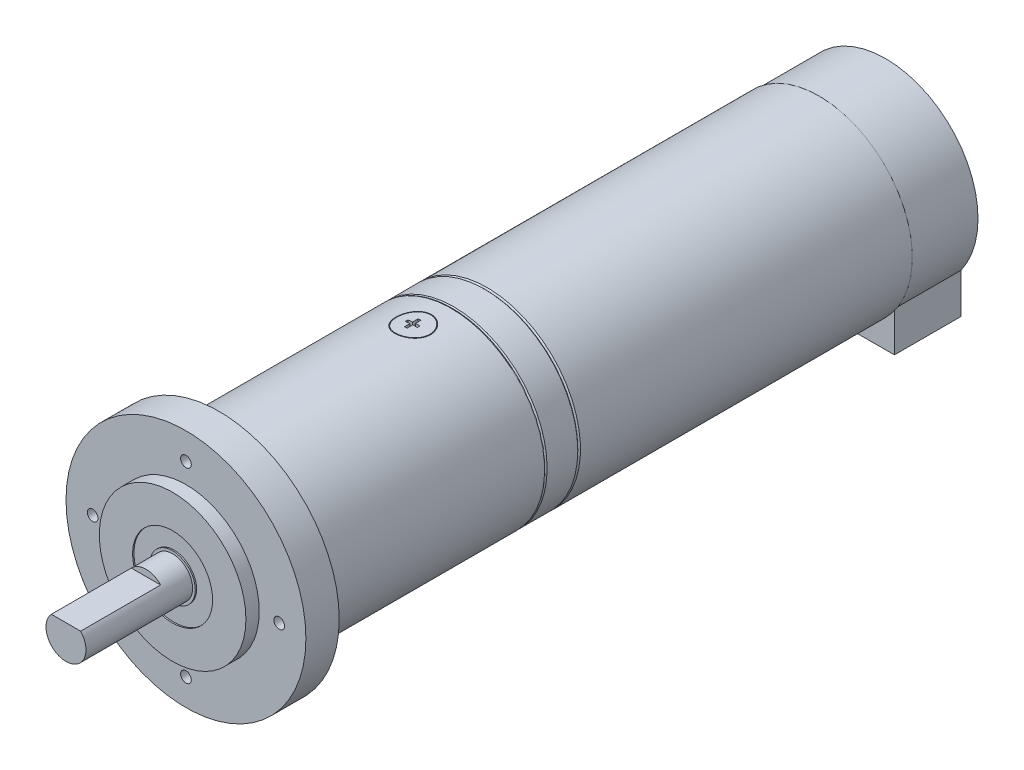
SolidWorks part; units mm, degrees
ref_plane "Front Plane" through (0, 0, 0) normal (0, 0, 1) x (1, 0, 0)
ref_plane "Top Plane" through (0, 0, 0) normal (0, 1, 0) x (1, 0, 0)
ref_plane "Right Plane" through (0, 0, 0) normal (1, 0, 0) x (0, 0, -1)
sketch "Sketch1" plane through (0, 0, 0) normal (0, 0, 1) x (1, 0, 0)
  circle A0 centre (0, 0) radius 18
  circle A1 centre (0, 0) radius 11
  dimension "D1" = 36
  dimension "D2" = 22
extrude "Boss-Extrude2" add sketch "Sketch1" against normal blind 5 contours A0
extrude "Boss-Extrude3" add sketch "Sketch1<4>" along normal blind 2 contours A1
sketch "Sketch1<4>" plane through (0, 0, 0) normal (0, 0, 1) x (1, 0, 0) same geometry as "Sketch1"
sketch "Sketch2" plane through (0, 0, 2) normal (0, 0, 1) x (1, 0, 0)
  circle A0 centre (0, 0) radius 3
  dimension "D1" = 6
extrude "Boss-Extrude4" add sketch "Sketch2" along normal blind 16 contours A0
sketch "Sketch3" plane through (0, 0, 18) normal (0, 0, 1) x (1, 0, 0)
  line L1 (-2.9161, 3.7933) -> (3.4469, 3.7933)
  line L2 (-2.9161, 3.7933) -> (-2.9161, 2.0435)
  line L3 (-2.9161, 2.0435) -> (3.4469, 2.0435)
  line L4 (3.4469, 3.7933) -> (3.4469, 2.0435)
extrude "Cut-Extrude1" cut sketch "Sketch3" against normal blind 12
sketch "Sketch4" plane through (0, 0, 2) normal (0, 0, 1) x (1, 0, 0)
  circle A0 centre (0, 0) radius 6
  circle A1 centre (0, 0) radius 3.4
  dimension "D1" = 12
  dimension "D2" = 6.8
extrude "Cut-Extrude2" cut sketch "Sketch4" against normal blind 0.2
sketch "Sketch5" plane through (0, 0, -5) normal (0, 0, -1) x (-1, 0, 0)
  circle A0 centre (0, 0) radius 14
  point P3 (0, 14)
  point P4 (-14, 0)
  point P5 (0, -14)
  point P6 (14, 0)
hole_wizard "Tap Drill for M2x0.4 Tap1" positions "3DSketch1" profile "Sketch6" hole size "M2x0.4" standard "ANSI Metric" end condition through all
sketch3d "3DSketch1"
  point P0 (0, 14, -5)
  point P3 (14, 0, -5)
  point P6 (0, -14, -5)
  point P9 (-14, 0, -5)
sketch "Sketch6" plane through (0, 14, -5) normal (1, 0, 0) x (0, 1, 0)
  line L0 (0, 0) -> (0, 23)
  line L1 (0, 23) -> (0.8, 23)
  line L2 (0.8, 23) -> (0.8, 0)
  line L5 (0.8, 0) -> (0, 0)
  line L11 (0, -6.35) -> (0, 107.95) construction
  dimension "Thru Hole Dia." = 1.6
  dimension "Thru Hole Depth" = 23
extrude "Boss-Extrude5" add sketch "Sketch5" along normal blind 35 contours A0
fillet "Fillet2" radius 0.2 1 edges at (-14, 0, -40)
sketch "Sketch7" plane through (0, 0, -40) normal (0, 0, -1) x (-1, 0, 0)
  circle A0 centre (0, 0) radius 14
extrude "Boss-Extrude6" add sketch "Sketch7" along normal blind 5
chamfer "Chamfer1" distance 0.2 angle 45 2 edges at (-14, 0, -45) (-14, 0, -40)
sketch "Sketch10" plane through (0, 0, -45) normal (0, 0, -1) x (-1, 0, 0)
  circle A0 centre (0, 0) radius 14
extrude "Boss-Extrude7" add sketch "Sketch10" along normal blind 50
chamfer "Chamfer2" distance 0.2 angle 45 1 edges at (-14, 0, -45)
sketch "Sketch11" plane through (0, 0, -95) normal (0, 0, -1) x (-1, 0, 0)
  line L2 (-11.3137, -8) -> (-11.3137, -14)
  line L3 (-11.3137, -14) -> (11.3137, -14)
  line L4 (11.3137, -8) -> (11.3137, -14)
  arc A0 (11.3137, -8) -> (-11.3137, -8) centre (0, 0) ccw
  circle A1 centre (0, 0) radius 18 construction
  dimension "D1" = 6
  dimension "D2" = 6
extrude "Boss-Extrude8" add sketch "Sketch11" along normal blind 10 separate body
ref_plane "Plane1" through (0, 14, 0) normal (0, 1, 0) x (1, 0, 0)
sketch "Sketch12" plane through (0, 14, 0) normal (0, 1, 0) x (1, 0, 0)
  circle A0 centre (-0.8303, 34.9357) radius 2.5
  circle A1 centre (-0.8303, 34.9357) radius 2.6
  dimension "D1" = 0.1
extrude "Cut-Extrude3" cut sketch "Sketch12" against normal blind 10.13
sketch "Sketch13" plane through (0, 14, 0) normal (0, 1, 0) x (1, 0, 0)
  line L0 (-0.7432, 35.174) -> (-0.0372, 35.174)
  line L1 (-1.8588, 34.7774) -> (-1.1577, 34.7774)
  line L2 (-1.8588, 34.7774) -> (-1.8588, 35.174)
  line L3 (-1.8588, 35.174) -> (-1.1577, 35.174)
  line L4 (-0.0372, 34.7774) -> (-0.0372, 35.174)
  line L5 (-1.1577, 33.9448) -> (-0.7432, 33.9448)
  line L6 (-1.1577, 33.9448) -> (-1.1577, 34.7774)
  line L7 (-1.1577, 35.9946) -> (-0.7432, 35.9946)
  line L8 (-0.7432, 33.9448) -> (-0.7432, 34.7774)
  line L9 (-0.7432, 34.7774) -> (-0.0372, 34.7774)
  line L10 (-1.1577, 35.174) -> (-1.1577, 35.9946)
  line L11 (-0.7432, 35.174) -> (-0.7432, 35.9946)
extrude "Cut-Extrude4" cut sketch "Sketch13" against normal blind 2
ref_plane "Plano1" through (0, 0, 0) normal (-1, 0, 0) x (0, 0, 1)
